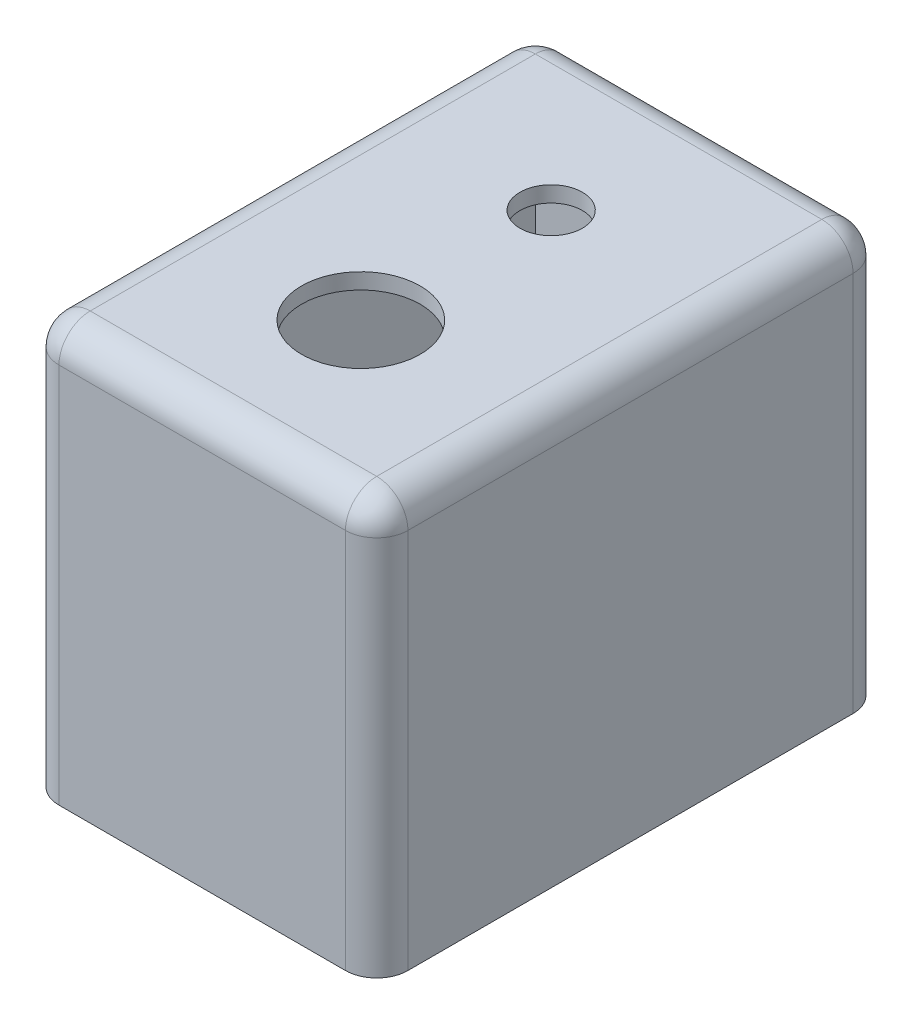
SolidWorks part; units mm, degrees
ref_plane "Front Plane" through (0, 0, 0) normal (0, 0, 1) x (1, 0, 0)
ref_plane "Top Plane" through (0, 0, 0) normal (0, 1, 0) x (1, 0, 0)
ref_plane "Right Plane" through (0, 0, 0) normal (1, 0, 0) x (0, 0, -1)
sketch "Sketch2" plane through (0, 0, 0) normal (0, 1, 0) x (1, 0, 0)
  line L1 (-27.94, 40.64) -> (27.94, 40.64)
  line L2 (-27.94, 40.64) -> (-27.94, -40.64)
  line L3 (-27.94, -40.64) -> (27.94, -40.64)
  line L4 (27.94, 40.64) -> (27.94, -40.64)
  line L5 (-27.94, 40.64) -> (27.94, -40.64) construction
  line L6 (-27.94, -40.64) -> (27.94, 40.64) construction
  line L7 (-25.4, 38.1) -> (25.4, 38.1)
  line L8 (-25.4, 38.1) -> (-25.4, -38.1)
  line L9 (-25.4, -38.1) -> (25.4, -38.1)
  line L10 (25.4, 38.1) -> (25.4, -38.1)
  line L11 (-25.4, 38.1) -> (25.4, -38.1) construction
  line L12 (-25.4, -38.1) -> (25.4, 38.1) construction
  point P0 (0, 0)
  point P6 (0, 0)
  dimension "D1" = 2.54
  dimension "D2" = 2.54
  dimension "D3" = 50.8
  dimension "D4" = 76.2
extrude "Boss-Extrude1" add sketch "Sketch2" along normal blind 63.5
sketch "Sketch3" plane through (0, 0, 0) normal (1, 0, 0) x (0, 0, -1)
  line L1 (-40.64, 63.5) -> (40.64, 63.5)
  line L2 (-40.64, 63.5) -> (-40.64, 66.04)
  line L3 (-40.64, 66.04) -> (40.64, 66.04)
  line L4 (40.64, 63.5) -> (40.64, 66.04)
  dimension "D1" = 2.54
extrude "Boss-Extrude2" add sketch "Sketch3" along normal through all and the other way through all
fillet "Fillet1" radius 5 4 edges at (27.94, 66.04, 0) (0, 66.04, 40.64) (-27.94, 66.04, 0) (0, 66.04, -40.64)
fillet "Fillet4" radius 5 2 edges at (-26.4755, 64.5755, -39.1755) (-27.94, 30.52, -40.64)
fillet "Fillet5" radius 5 2 edges at (26.4755, 64.5755, -39.1755) (27.94, 30.52, -40.64)
fillet "Fillet6" radius 5 2 edges at (26.4755, 64.5755, 39.1755) (27.94, 30.52, 40.64)
fillet "Fillet7" radius 5 2 edges at (-26.4755, 64.5755, 39.1755) (-27.94, 30.52, 40.64)
sketch "Sketch4" plane through (0, 0, 0) normal (0, 1, 0) x (1, 0, 0)
  line L0 (0, 68.5301) -> (0, -64.9409) construction
  line L1 (-55.4073, 15.24) -> (64.8288, 15.24) construction
  line L2 (-55.4073, -15.24) -> (64.8288, -15.24) construction
  line L3 (-22.94, 40.64) -> (22.94, 40.64) construction
  line L4 (22.94, -40.64) -> (-22.94, -40.64) construction
  circle A0 centre (0, 15.24) radius 5
  circle A1 centre (0, -15.24) radius 9.5
  dimension "D3" = 10
  dimension "D4" = 19
  dimension "D1" = 25.4
  dimension "D2" = 25.4
extrude "Cut-Extrude1" cut sketch "Sketch4" along normal up to next
sketch "Sketch6" plane through (0, 0, -40.64) normal (0, 0, -1) x (-1, 0, 0)
  line L0 (0, 0) -> (0, 136.4181) construction
  line L1 (-22.94, 0) -> (22.94, 0) construction
  circle A0 centre (0, 0) radius 10
  dimension "D1" = 20
extrude "Cut-Extrude2" cut sketch "Sketch6" against normal up to next
